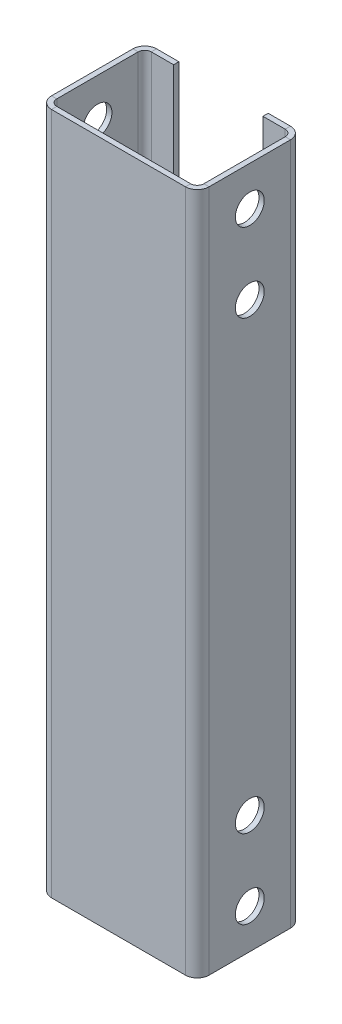
SolidWorks part; units mm, degrees
note: The reader was unsure of these and kept them because the rebuilt part matched: flange length of "Edge-Flange1", "Edge-Flange2".
material "AISI 304"
ref_plane "Front Plane" through (0, 0, 0) normal (0, 0, 1) x (1, 0, 0)
ref_plane "Top Plane" through (0, 0, 0) normal (0, 1, 0) x (1, 0, 0)
ref_plane "Right Plane" through (0, 0, 0) normal (1, 0, 0) x (0, 0, -1)
sketch "Sketch1" plane through (0, 0, 0) normal (0, 0, 1) x (1, 0, 0)
  line L1 (-30, -130) -> (30, -130)
  line L2 (-30, -130) -> (-30, 130)
  line L3 (-30, 130) -> (30, 130)
  line L4 (30, -130) -> (30, 130)
  line L5 (-30, -130) -> (30, 130) construction
  line L6 (-30, 130) -> (30, -130) construction
  point P0 (0, 0)
  dimension "D1" = 260
  dimension "D2" = 60
base flange "Base-Flange1" sketch "Sketch1" thickness 2 reverse thickness direction no parameters "D1"=2.5
edge flange "Edge-Flange1" sketch "Sketch10" flange profiles "Sketch10", "Sketch11" flange angle 90 flange length 40 flange position material inside bend radius 2.5 thickness 2 relief obround parameters "D6"=10, "D8"=1
sketch "Sketch10" plane through (30, 0, -2) normal (-1, 0, 0) x (0, 1, 0)
  line L2 (-130, 0) -> (-130, 38)
  line L3 (-130, 38) -> (130, 38)
  line L4 (130, 38) -> (130, 0)
  line L5 (130, 0) -> (-130, 0) construction
  line L6 (130, 0) -> (-130, 0)
sketch "Sketch11" plane through (-30, 0, -2) normal (1, 0, 0) x (0, -1, 0)
  line L2 (-130, 0) -> (-130, 38)
  line L3 (-130, 38) -> (130, 38)
  line L4 (130, 38) -> (130, 0)
  line L5 (130, 0) -> (-130, 0) construction
  line L6 (130, 0) -> (-130, 0)
bend "EdgeBend1" bend radius 2.5 bend angle 90 parameters "D5"=1
bend "EdgeBend2" bend radius 2.5 bend angle 90 parameters "D5"=2
edge flange "Edge-Flange2" sketch "Sketch16" flange profiles "Sketch16", "Sketch17" flange angle 90 flange length 13 flange position material inside bend radius 2.5 thickness 2 relief obround parameters "D6"=10, "D8"=1
sketch "Sketch16" plane through (28, 0, -40) normal (0, 0, -1) x (0, -1, 0)
  line L2 (-130, 0) -> (-130, 11)
  line L3 (-130, 11) -> (130, 11)
  line L4 (130, 11) -> (130, 0)
  line L7 (-130, 0) -> (130, 0) construction
  line L8 (-130, 0) -> (130, 0)
sketch "Sketch17" plane through (-28, 0, -40) normal (0, 0, -1) x (0, 1, 0)
  line L2 (-130, 0) -> (-130, 11)
  line L3 (-130, 11) -> (130, 11)
  line L4 (130, 11) -> (130, 0)
  line L7 (-130, 0) -> (130, 0) construction
  line L8 (-130, 0) -> (130, 0)
bend "EdgeBend3" bend radius 2.5 bend angle 90 parameters "D5"=3
bend "EdgeBend4" bend radius 2.5 bend angle 90 parameters "D5"=4
sketch "Sketch18" plane through (30, 0, 0) normal (1, 0, 0) x (0, 0, -1)
  line L0 (4.5, -130) -> (35.5, -130) construction
  line L2 (35.5, -130) -> (4.5, -130) construction
  circle A0 centre (20, -115) radius 5.5
  circle A1 centre (20, -85) radius 5.5
  point P7 (20, -130)
  dimension "D1" = 11
  dimension "D2" = 30
  dimension "D3" = 15
  dimension "D4" = 0
extrude "Cut-Extrude1" cut sketch "Sketch18" against normal through all and the other way through all normal cut yes
mirror "Mirror1" about plane through (0, 0, 0) normal (0, 1, 0) of "Cut-Extrude1"
sketch "Bend-Lines1" [suppressed] plane through (0, 0, 0) normal (0, 1, 0) x (1, 0, 0)
sketch "Bounding-Box1" [suppressed] plane through (0, 0, 0) normal (0, 1, 0) x (1, 0, 0)
sheet metal parameters "Sheet-Metal1" thickness 2 parameters "D1"=2.5
flat pattern "Flat-Pattern1" [suppressed]
sketch "Bend-Lines2" plane through (0, 0, 0) normal (0, 1, 0) x (1, 0, 0)
sketch3d "Bounding-Box2" [suppressed]
  line L0 (-20, 1400, 0) -> (-20, -1400, 0) construction
  line L1 (20, 1400, 0) -> (20, -1400, 0) construction
  line L2 (-20, 1400, 0) -> (20, 1400, 0) construction
  line L3 (-20, -1400, 0) -> (20, -1400, 0) construction
sheet metal parameters "Sheet-Metal2" thickness 2 parameters "D1"=2.5
flat pattern "Flat-Pattern1"
sketch "Bend-Lines2" plane through (0, 0, 0) normal (0, 0, 1) x (1, 0, 0)
  line L0 (-18.0918, 1400) -> (-18.0918, -1400) construction
  line L1 (18.0918, -1400) -> (18.0918, 1400) construction
  line L2 (-18.0918, 1400) -> (-18.0918, -1400) construction
  line L3 (18.0918, -1400) -> (18.0918, 1400) construction
sketch3d "Bounding-Box2" [suppressed]
  line L0 (46.1836, 1400, 0) -> (46.1836, -1400, 0) construction
  line L1 (-46.1836, 1400, 0) -> (-46.1836, -1400, 0) construction
  line L2 (46.1836, 1400, 0) -> (-46.1836, 1400, 0) construction
  line L3 (46.1836, -1400, 0) -> (-46.1836, -1400, 0) construction
bend of the flat pattern "Flatten-<EdgeBend1>1"
bend of the flat pattern "Flatten-<EdgeBend2>1"
sheet metal parameters "Sheet-Metal3" thickness 2 parameters "D1"=2.5
flat pattern "Flat-Pattern1"
sketch "Bend-Lines2" plane through (0, 0, 0) normal (0, 0, 1) x (1, 0, 0)
  line L0 (-18.0918, 1400) -> (-18.0918, -1400) construction
  line L1 (18.0918, -1400) -> (18.0918, 1400) construction
  line L2 (-18.0918, 1400) -> (-18.0918, -1400) construction
  line L3 (18.0918, -1400) -> (18.0918, 1400) construction
  line L4 (-44.2754, 1400) -> (-44.2754, -1400) construction
  line L5 (44.2754, -1400) -> (44.2754, 1400) construction
  line L6 (-44.2754, 1400) -> (-44.2754, -1400) construction
  line L7 (44.2754, -1400) -> (44.2754, 1400) construction
sketch3d "Bounding-Box2" [suppressed]
  line L0 (57.3673, 1400, 0) -> (57.3673, -1400, 0) construction
  line L1 (-57.3673, 1400, 0) -> (-57.3673, -1400, 0) construction
  line L2 (57.3673, 1400, 0) -> (-57.3673, 1400, 0) construction
  line L3 (57.3673, -1400, 0) -> (-57.3673, -1400, 0) construction
bend of the flat pattern "Flatten-<EdgeBend1>1"
bend of the flat pattern "Flatten-<EdgeBend2>1"
bend of the flat pattern "Flatten-<EdgeBend3>1"
bend of the flat pattern "Flatten-<EdgeBend4>1"
sheet metal parameters "Sheet-Metal4" thickness 2 parameters "D1"=2.5
flat pattern "Flat-Pattern1"
sketch "Bend-Lines2" plane through (0, 0, 0) normal (0, 0, 1) x (1, 0, 0)
  line L0 (-18.0918, 1400) -> (-18.0918, -1400) construction
  line L1 (18.0918, -1400) -> (18.0918, 1400) construction
  line L2 (-18.0918, 1400) -> (-18.0918, -1400) construction
  line L3 (18.0918, -1400) -> (18.0918, 1400) construction
  line L4 (-44.2754, 1400) -> (-44.2754, -1400) construction
  line L5 (44.2754, -1400) -> (44.2754, 1400) construction
  line L6 (-44.2754, 1400) -> (-44.2754, -1400) construction
  line L7 (44.2754, -1400) -> (44.2754, 1400) construction
sketch3d "Bounding-Box2" [suppressed]
  line L0 (57.3673, 1400, 0) -> (57.3673, -1400, 0) construction
  line L1 (-57.3673, 1400, 0) -> (-57.3673, -1400, 0) construction
  line L2 (57.3673, 1400, 0) -> (-57.3673, 1400, 0) construction
  line L3 (57.3673, -1400, 0) -> (-57.3673, -1400, 0) construction
bend of the flat pattern "Flatten-<EdgeBend1>1"
bend of the flat pattern "Flatten-<EdgeBend2>1"
bend of the flat pattern "Flatten-<EdgeBend3>1"
bend of the flat pattern "Flatten-<EdgeBend4>1"
sheet metal parameters "Sheet-Metal5" thickness 2 parameters "D1"=2.5
flat pattern "Flat-Pattern1"
sketch "Bend-Lines2" plane through (0, 0, 0) normal (0, 0, 1) x (1, 0, 0)
  line L0 (-28.0918, 130) -> (-28.0918, -130) construction
  line L1 (28.0918, -130) -> (28.0918, 130) construction
  line L2 (-28.0918, 130) -> (-28.0918, -130) construction
  line L3 (28.0918, -130) -> (28.0918, 130) construction
  line L4 (-64.2754, 130) -> (-64.2754, -130) construction
  line L5 (64.2754, -130) -> (64.2754, 130) construction
  line L6 (-64.2754, 130) -> (-64.2754, -130) construction
  line L7 (64.2754, -130) -> (64.2754, 130) construction
sketch3d "Bounding-Box2" [suppressed]
  line L0 (75.3673, 130, 0) -> (75.3673, -130, 0) construction
  line L1 (-75.3673, 130, 0) -> (-75.3673, -130, 0) construction
  line L2 (75.3673, 130, 0) -> (-75.3673, 130, 0) construction
  line L3 (75.3673, -130, 0) -> (-75.3673, -130, 0) construction
bend of the flat pattern "Flatten-<EdgeBend1>1"
bend of the flat pattern "Flatten-<EdgeBend2>1"
bend of the flat pattern "Flatten-<EdgeBend3>1"
bend of the flat pattern "Flatten-<EdgeBend4>1"
